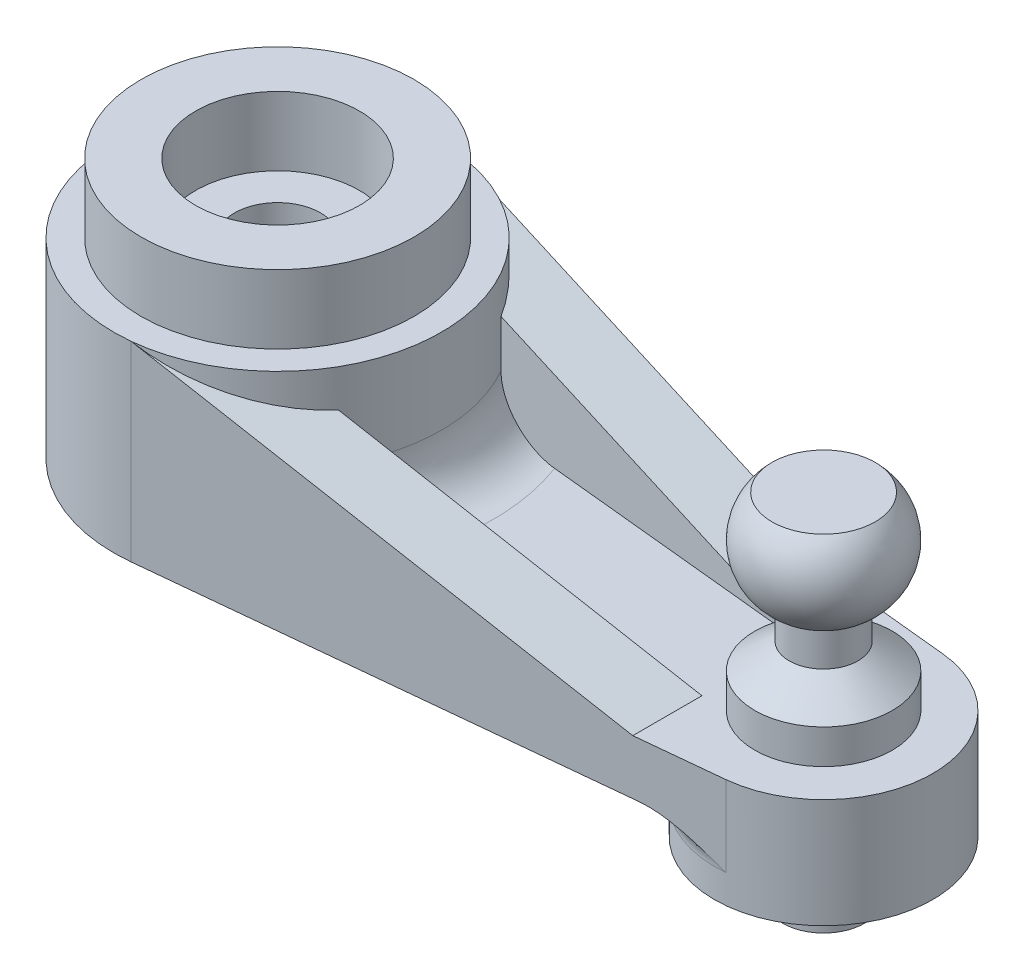
SolidWorks part; units mm, degrees
ref_plane "Front Plane" through (0, 0, 0) normal (0, 0, 1) x (1, 0, 0)
ref_plane "Top Plane" through (0, 0, 0) normal (0, 1, 0) x (1, 0, 0)
ref_plane "Right Plane" through (0, 0, 0) normal (1, 0, 0) x (0, 0, -1)
sketch "Sketch1" plane through (0, 0, 0) normal (0, 1, 0) x (1, 0, 0)
  line L0 (15.875, 0) -> (0, 0) construction
  line L1 (-4.7625, 0) -> (-4.7625, 5.5654) construction
  line L2 (19.05, 0) -> (19.05, 7.1802) construction
  line L3 (16.1925, 3.1591) -> (0.4762, 4.7386)
  line L4 (0.4763, -4.7386) -> (16.1925, -3.1591)
  circle A0 centre (0, 0) radius 4.7625
  circle A1 centre (15.875, 0) radius 3.175
  dimension "D1" = 9.525
  dimension "D2" = 6.35
  dimension "D3" = 23.8125
extrude "Boss-Extrude1" add sketch "Sketch1" along normal blind 5.5562 contours A0 | A1 L3 A0 L4 | A1 region at (8.463, 0, 0) region at (15.875, 0, 0) region at (0, 0, 0)
sketch "Sketch2" plane through (0, 0, 0) normal (0, 0, 1) x (1, 0, 0)
  line L0 (0.4763, 5.5562) -> (13.7336, 1.5875)
  line L1 (13.7336, 1.5875) -> (16.1925, 1.5875)
  line L2 (16.1925, 5.5562) -> (16.1925, 0) construction
  line L3 (16.1925, 1.5875) -> (19.05, 1.5875)
  line L4 (19.05, 0) -> (19.05, 5.5562) construction
  line L5 (19.05, 1.5875) -> (19.05, 5.5562)
  line L6 (19.05, 5.5562) -> (0.4763, 5.5562)
  line L7 (0.4763, 0) -> (16.1925, 0) construction
  line L8 (19.05, 5.5562) -> (19.05, 1.5875)
  point P13 (14.4315, 1.5875)
  point P14 (13.7336, 1.5875)
  dimension "D1" = 1.5875
extrude "Cut-Extrude1" cut sketch "Sketch2" against normal through all and the other way through all contours L5 L6 L0 L1 L3 region at (12.4644, 3.9389, 0)
sketch "Sketch3" plane through (0, 5.5562, 0) normal (0, 1, 0) x (1, 0, 0)
  circle A0 centre (0, 0) radius 4.7625
extrude "Boss-Extrude2" add sketch "Sketch3" against normal up to surface (5.5563 mm away) up to face at (7.7391, 0, 0)
sketch "Sketch4" plane through (0, 5.5562, 0) normal (0, 1, 0) x (1, 0, 0)
  circle A0 centre (0, 0) radius 3.9688
  circle A1 centre (0, 0) radius 2.3813
  dimension "D1" = 7.9375
  dimension "D2" = 4.7625
extrude "Boss-Extrude3" add sketch "Sketch4" along normal blind 2
sketch "Sketch5" plane through (0, 1.5875, 0) normal (0, 1, 0) x (1, 0, 0)
  line L0 (13.7336, 1.3961) -> (4.1362, 2.3607)
  line L1 (13.7336, 3.4062) -> (13.7336, -3.4062) construction
  line L2 (13.7336, -1.3961) -> (4.1362, -2.3607)
  line L3 (13.7336, -3.4062) -> (0.4763, -4.7386) construction
  line L4 (0.4762, 4.7386) -> (13.7336, 3.4062) construction
  line L5 (13.7336, 1.3961) -> (13.7336, -1.3961)
  line L6 (13.7336, 0) -> (19.05, 0) construction
  arc A0 (0.4763, -4.7386) -> (0.4762, 4.7386) centre (0, 0) ccw construction
  arc A1 (16.1925, -3.1591) -> (16.1925, 3.1591) centre (15.875, 0) ccw construction
  arc A3 (4.1362, 2.3607) -> (4.1362, -2.3607) centre (0, 0) cw
  point P13 (7.1049, 4.0724)
  line M6 (13.7336, 3.4062) -> (13.7336, -3.4062)
  dimension "D1" = 2
extrude "Cut-Extrude2" cut sketch "Sketch5" along normal up to surface (3.9688 mm away) contours L0 A3 L2 L5 M6 region at (8.7669, 1.5875, 0) up to face at (0, 5.5562, 3.9688)
sketch "Sketch6" plane through (0, 0, 0) normal (0, -1, 0) x (1, 0, 0)
  circle A0 centre (0, 0) radius 3.5719
  dimension "D1" = 7.1437
extrude "Cut-Extrude3" cut sketch "Sketch6" against normal blind 3
sketch "Sketch7" plane through (0, 3, 0) normal (0, -1, 0) x (1, 0, 0)
  circle A0 centre (0, 0) radius 1.25
  dimension "D1" = 2.5
extrude "Cut-Extrude4" cut sketch "Sketch7" against normal through all
sketch "Sketch8" plane through (0, 0, 0) normal (0, -1, 0) x (1, 0, 0)
  circle A0 centre (15.875, 0) radius 3.175
extrude "Boss-Extrude4" add sketch "Sketch8" along normal blind 1.5875
fillet "Fillet1" radius 0.75 1 edges at (12.7, 0, 0)
ref_axis "Axis1" through (15.875, 1.5875, 0) along (0, -1, 0)
sketch "Sketch9" plane through (0, 0, 0) normal (0, 0, 1) x (1, 0, 0)
  line L0 (15.875, -1.5875) -> (15.875, -3.175)
  line L1 (12.7, -1.5875) -> (19.05, -1.5875) construction
  line L2 (15.875, 1.5875) -> (15.875, -1.5875) construction
  line L3 (15.875, -3.175) -> (17.0656, -3.175)
  line L4 (17.0656, -3.175) -> (17.0656, -1.5875)
  line L5 (17.0656, -1.5875) -> (15.875, -1.5875)
  line L6 (15.875, 1.5875) -> (15.875, 7.0875)
  line L7 (15.875, 1.5875) -> (17.875, 1.5875)
  line L8 (17.875, 1.5875) -> (17.875, 2.5875)
  line L9 (17.875, 2.5875) -> (16.875, 3.3375)
  line L10 (16.875, 3.3375) -> (16.875, 4.3375)
  line L11 (19.05, 1.5875) -> (16.1925, 1.5875) construction
  line L12 (15.875, 7.0875) -> (17.375, 7.0875)
  line L13 (17.875, 5.8847) -> (17.875, 8.0628) construction
  arc A0 (17.375, 7.0875) -> (16.875, 4.3375) centre (16.1782, 5.8847) cw
  dimension "D1" = 1.5875
  dimension "D2" = 1.1906
  dimension "D3" = 2
  dimension "D4" = 1
  dimension "D5" = 0.75
  dimension "D6" = 1
  dimension "D7" = 5.5
  dimension "D8" = 1
  dimension "D9" = 1.5
  dimension "D10" = 2
revolve "Revolve1" add sketch "Sketch9" angle 360 about axis through (15.875, 1.5875, 0) along (0, -1, 0)
fillet "Fillet2" radius 1.5 1 edges at (4.7625, 1.5875, 0)
ref_point "Point1"
